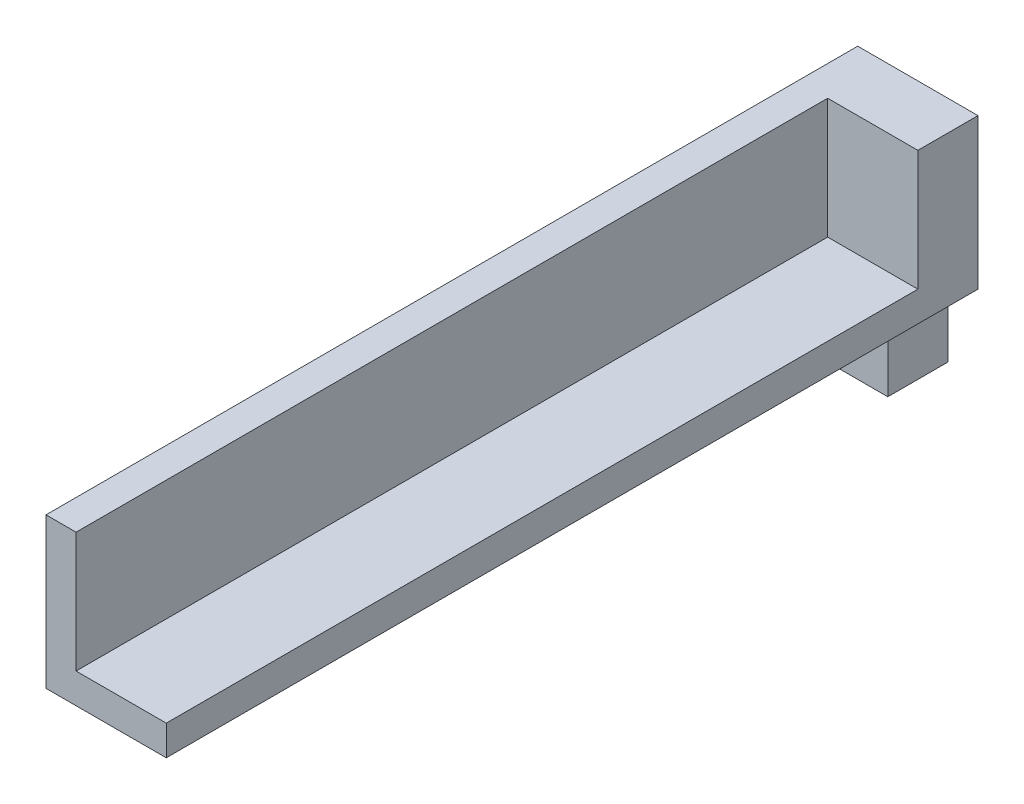
SolidWorks part; units mm, degrees
ref_plane "Front Plane" through (0, 0, 0) normal (0, 0, 1) x (1, 0, 0)
ref_plane "Top Plane" through (0, 0, 0) normal (0, 1, 0) x (1, 0, 0)
ref_plane "Right Plane" through (0, 0, 0) normal (1, 0, 0) x (0, 0, -1)
sketch "Sketch1" plane through (0, 0, 0) normal (1, 0, 0) x (0, 0, -1)
  line L0 (0, -1509.5556) -> (0, 73968.222) construction
  line L1 (0, 0) -> (-10, 0)
  line L2 (-10, 0) -> (-10, -20)
  line L3 (-10, -20) -> (-30, -20)
  line L6 (0, -38) -> (0, 0)
  line L7 (-30, -20) -> (-30, -25)
  line L8 (-30, -25) -> (-10, -25)
  line L9 (-10, -25) -> (-10, -38)
  line L10 (-10, -38) -> (0, -38)
  dimension "D1" = 20
  dimension "D2" = 20
  dimension "D3" = 5
  dimension "D4" = 10
  dimension "D5" = 10
  dimension "D6" = 38
extrude "Boss-Extrude1" add sketch "Sketch1" along normal blind 10
sketch "Sketch2" plane through (0, 0, 0) normal (-1, 0, 0) x (0, 0, 1)
  line L1 (0, 0) -> (30, 0)
  line L2 (0, 0) -> (0, -25)
  line L3 (0, -25) -> (30, -25)
  line L4 (30, 0) -> (30, -25)
extrude "Boss-Extrude2" add sketch "Sketch2" along normal blind 5
sketch "Sketch3" plane through (10, 0, 0) normal (1, 0, 0) x (0, 0, -1)
  line L0 (-10, 0) -> (-10, -20)
  line L1 (-10, -20) -> (-30, -20)
  line L2 (-30, -20) -> (-30, -25)
  line L3 (-30, -25) -> (-10, -25)
  line L4 (-10, -25) -> (0, -25)
  line L5 (0, -25) -> (0, 0)
  line L6 (0, 0) -> (-10, 0)
extrude "Boss-Extrude3" add sketch "Sketch3" along normal blind 5
sketch "Sketch4" plane through (0, 0, 30) normal (0, 0, 1) x (1, 0, 0)
  line L0 (-5, 0) -> (-5, -25)
  line L1 (-5, -25) -> (15, -25)
  line L2 (15, -25) -> (15, -20)
  line L3 (15, -20) -> (0, -20)
  line L4 (0, -20) -> (0, 0)
  line L5 (0, 0) -> (-5, 0)
extrude "Boss-Extrude4" add sketch "Sketch4" along normal up to surface (105 mm away) up to face at (3.3333, -15, 30)
